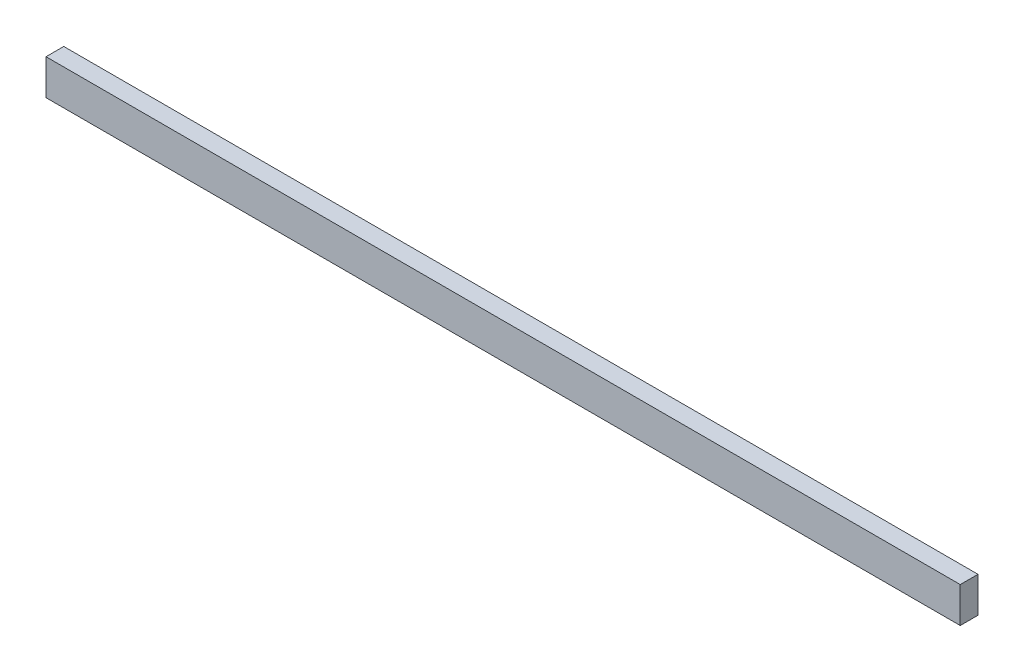
SolidWorks part; units mm, degrees
material "Pine"
ref_plane "Front Plane" through (0, 0, 0) normal (0, 0, 1) x (1, 0, 0)
ref_plane "Top Plane" through (0, 0, 0) normal (0, 1, 0) x (1, 0, 0)
ref_plane "Right Plane" through (0, 0, 0) normal (1, 0, 0) x (0, 0, -1)
sketch "Sketch1" plane through (0, 0, 0) normal (1, 0, 0) x (0, 0, -1)
  line L1 (0, 0) -> (40, 0)
  line L2 (0, 0) -> (0, 80)
  line L3 (0, 80) -> (40, 80)
  line L4 (40, 0) -> (40, 80)
  dimension "D1" = 80
  dimension "D2" = 40
extrude "Boss-Extrude1" add sketch "Sketch1" along normal blind 2060
